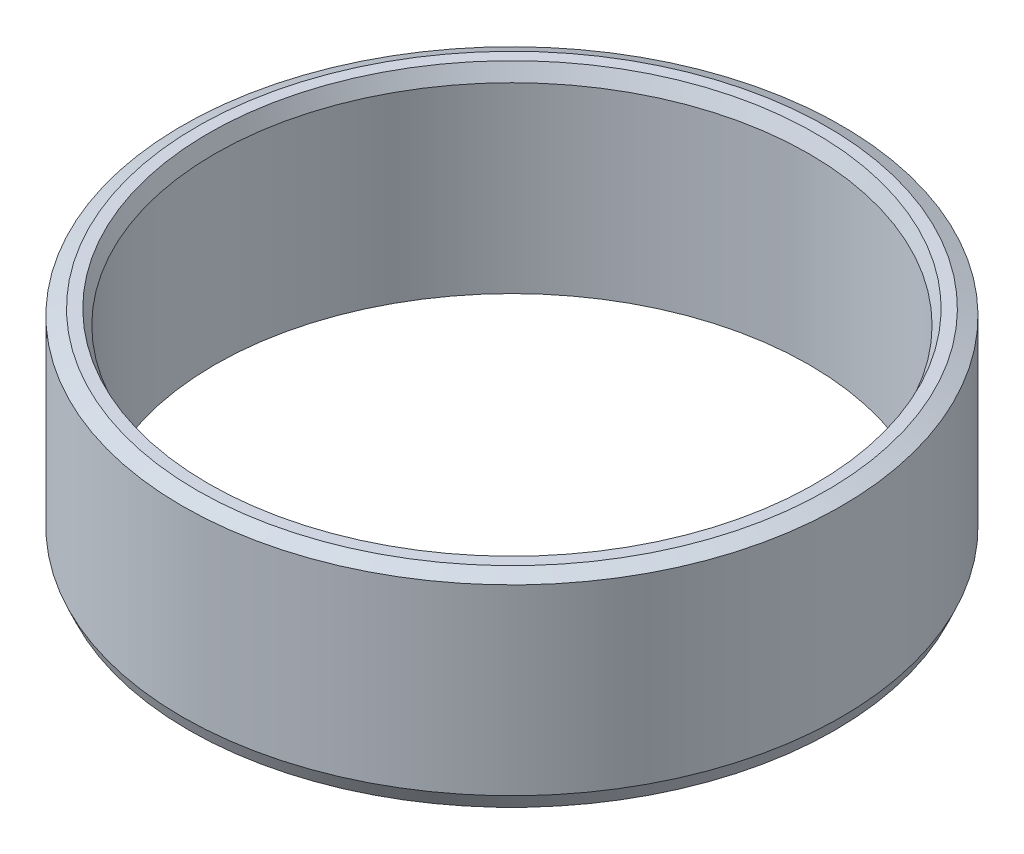
SolidWorks part; units mm, degrees
ref_plane "Front Plane" through (0, 0, 0) normal (0, 0, 1) x (1, 0, 0)
ref_plane "Top Plane" through (0, 0, 0) normal (0, 1, 0) x (1, 0, 0)
ref_plane "Right Plane" through (0, 0, 0) normal (1, 0, 0) x (0, 0, -1)
sketch "Sketch1" plane through (0, 0, 0) normal (0, 1, 0) x (1, 0, 0)
  circle A0 centre (0, 0) radius 47.5
  dimension "SLEEVE_OD" = 95
extrude "Boss-Extrude1" add sketch "Sketch1" along normal blind 29.338
sketch "Sketch2" plane through (0, 0, 0) normal (0, 1, 0) x (1, 0, 0)
  circle A0 centre (0, 0) radius 42.8213
  dimension "BORE_D" = 85.6426
extrude "Cut-Extrude1" cut sketch "Sketch2" along normal through all
chamfer "Chamfer1" distance 0.9179 angle 66.39 4 edges at (0, 29.338, 42.8213) (0, 0, 42.8213) (0, 0, 47.5) (0, 29.338, 47.5) first distance on face at (0, 29.338, 42.8213) first distance on face at (0, 0, 42.8213) first distance on face at (0, 29.338, 47.5)
